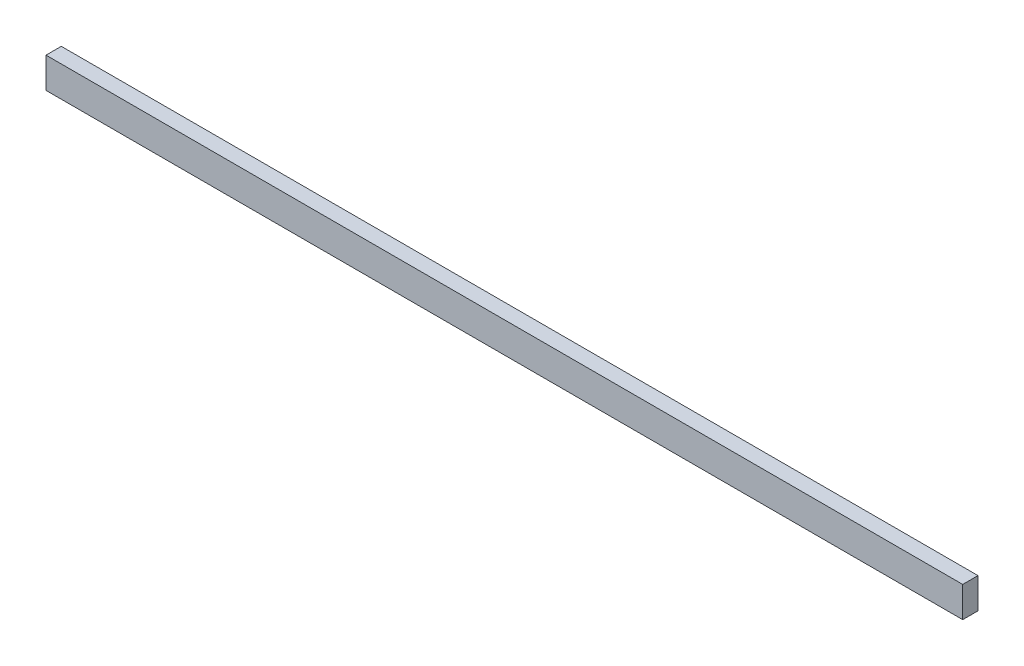
SolidWorks part; units mm, degrees
ref_plane "Front Plane" through (0, 0, 0) normal (0, 0, 1) x (1, 0, 0)
ref_plane "Top Plane" through (0, 0, 0) normal (0, 1, 0) x (1, 0, 0)
ref_plane "Right Plane" through (0, 0, 0) normal (1, 0, 0) x (0, 0, -1)
other "Configuration Table"
sketch "Sketch1" plane through (0, 0, 0) normal (0, 0, 1) x (1, 0, 0)
  line L1 (0, 0) -> (152.4, 0)
  line L2 (0, 0) -> (0, 5.08)
  line L3 (0, 5.08) -> (152.4, 5.08)
  line L4 (152.4, 0) -> (152.4, 5.08)
sheet metal parameters "Sheet-Metal1" thickness 2.54 parameters "D1"=0.7366
base flange "Base-Flange1" sketch "Sketch1" thickness 2.54 reverse thickness direction yes parameters "D1"=0.7366
flat pattern "Flat-Pattern1" [suppressed]
sketch "Bend-Lines1" plane through (0, 0, 0) normal (0, 1, 0) x (-1, 0, 0)
